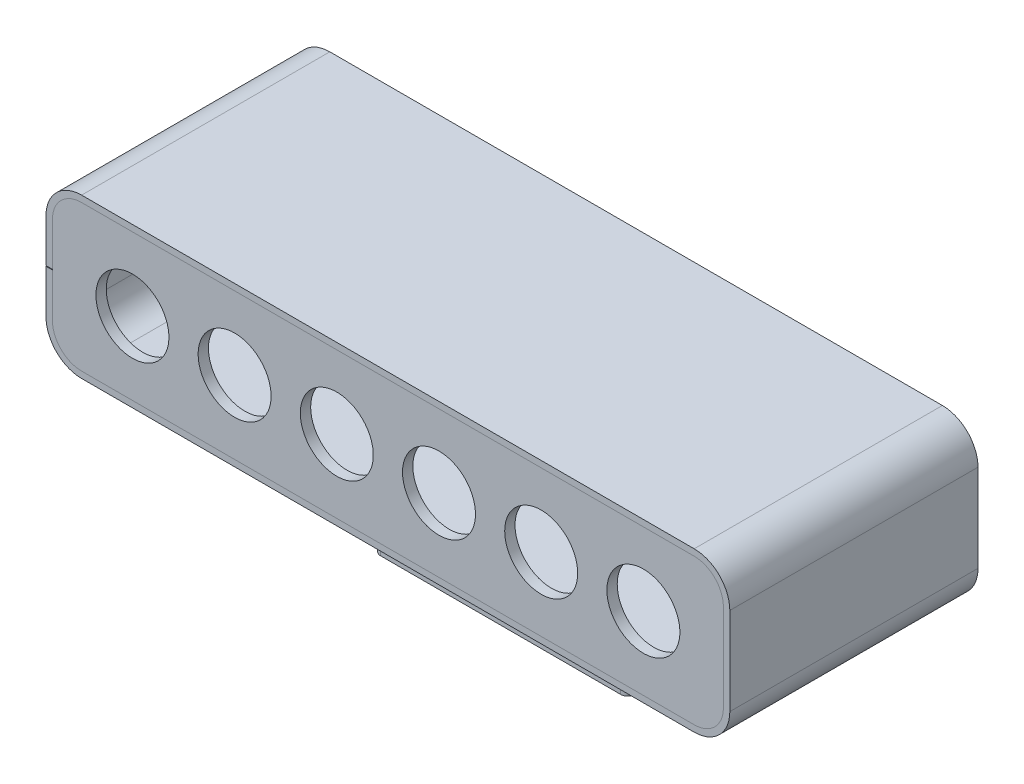
SolidWorks part; units mm, degrees
material "Acrylic (Medium-high impact)"
ref_plane "Front" through (0, 0, 0) normal (0, 0, 1) x (1, 0, 0)
ref_plane "Top" through (0, 0, 0) normal (0, 1, 0) x (1, 0, 0)
ref_plane "Right" through (0, 0, 0) normal (1, 0, 0) x (0, 0, -1)
sketch "Sketch5" plane through (0, 0, 0) normal (0, 1, 0) x (1, 0, 0)
  line L1 (0, 0) -> (-692.15, 0)
  line L2 (0, 0) -> (0, 107.95)
  line L3 (0, 107.95) -> (-692.15, 107.95)
  line L4 (-692.15, 0) -> (-692.15, 107.95)
  dimension "D1" = 107.95
  dimension "D2" = 692.15
extrude "Boss-Extrude4" [suppressed] add sketch "Sketch5" along normal blind 2.794
sketch "Sketch1" plane through (0, 0, 0) normal (0, 0, 1) x (1, 0, 0)
  line L1 (-145.923, 31.75) -> (145.923, 31.75)
  line L2 (-145.923, 31.75) -> (-145.923, -31.75)
  line L3 (-145.923, -31.75) -> (145.923, -31.75)
  line L4 (145.923, 31.75) -> (145.923, -31.75)
  line L5 (-145.923, 31.75) -> (145.923, -31.75) construction
  line L6 (-145.923, -31.75) -> (145.923, 31.75) construction
  point P0 (0, 0)
  dimension "D1" = 291.846
  dimension "D2" = 63.5
extrude "Boss-Extrude1" add sketch "Sketch1" along normal blind 4.4958
fillet "Fillet1" radius 12.7 4 edges at (-145.923, -31.75, 2.2479) (145.923, -31.75, 2.2479) (145.923, 31.75, 2.2479) (-145.923, 31.75, 2.2479)
sketch "Sketch3" plane through (0, 0, 0) normal (0, 0, 1) x (1, 0, 0)
  line L0 (133.223, 34.544) -> (-133.223, 34.544)
  line L1 (-148.717, 19.05) -> (-148.717, 0.254)
  line L2 (-133.223, -34.544) -> (133.223, -34.544)
  line L3 (148.717, -19.05) -> (148.717, 19.05)
  line L4 (-133.223, -31.75) -> (133.223, -31.75)
  line L5 (-145.923, 19.05) -> (-145.923, -19.05)
  line L6 (133.223, 31.75) -> (-133.223, 31.75)
  line L7 (145.923, -19.05) -> (145.923, 19.05)
  line L8 (-133.223, -31.75) -> (133.223, -31.75)
  line L9 (-145.923, 19.05) -> (-145.923, 0.254)
  line L10 (133.223, 31.75) -> (-133.223, 31.75)
  line L11 (145.923, -19.05) -> (145.923, 19.05)
  line L12 (-145.923, 0) -> (-148.717, 0)
  line L13 (-145.923, 0.254) -> (-148.717, 0.254)
  line L14 (-145.923, 0) -> (-145.923, -19.05)
  line L15 (-145.923, 19.05) -> (-145.923, -19.05) construction
  line L16 (-148.717, 0) -> (-148.717, -19.05)
  line L17 (-148.717, 19.05) -> (-148.717, -19.05) construction
  line L18 (-145.923, 19.05) -> (-145.923, -19.05) construction
  arc A0 (-133.223, 34.544) -> (-148.717, 19.05) centre (-133.223, 19.05) ccw
  arc A1 (-148.717, -19.05) -> (-133.223, -34.544) centre (-133.223, -19.05) ccw
  arc A2 (133.223, -34.544) -> (148.717, -19.05) centre (133.223, -19.05) ccw
  arc A3 (148.717, 19.05) -> (133.223, 34.544) centre (133.223, 19.05) ccw
  arc A4 (-145.923, -19.05) -> (-133.223, -31.75) centre (-133.223, -19.05) ccw
  arc A5 (-133.223, 31.75) -> (-145.923, 19.05) centre (-133.223, 19.05) ccw
  arc A6 (145.923, 19.05) -> (133.223, 31.75) centre (133.223, 19.05) ccw
  arc A7 (133.223, -31.75) -> (145.923, -19.05) centre (133.223, -19.05) ccw
  arc A8 (-145.923, -19.05) -> (-133.223, -31.75) centre (-133.223, -19.05) ccw
  arc A9 (-133.223, 31.75) -> (-145.923, 19.05) centre (-133.223, 19.05) ccw
  arc A10 (145.923, 19.05) -> (133.223, 31.75) centre (133.223, 19.05) ccw
  arc A11 (133.223, -31.75) -> (145.923, -19.05) centre (133.223, -19.05) ccw
  dimension "D3" = 0.254
  dimension "D1" = 0
  dimension "D2" = 2.794
extrude "Boss-Extrude2" add sketch "Sketch3" along normal blind 107.95 separate body
sketch "Sketch4" plane through (0, 0, 107.95) normal (0, 0, 1) x (1, 0, 0)
  line L4 (-145.923, 19.05) -> (-145.923, -19.05)
  line L5 (-133.223, -31.75) -> (133.223, -31.75)
  line L6 (145.923, -19.05) -> (145.923, 19.05)
  line L7 (133.223, 31.75) -> (-133.223, 31.75)
  line L8 (-145.923, 19.05) -> (-145.923, -19.05)
  line L9 (-133.223, -31.75) -> (133.223, -31.75)
  line L10 (145.923, -19.05) -> (145.923, 19.05)
  line L11 (133.223, 31.75) -> (-133.223, 31.75)
  arc A4 (-145.923, -19.05) -> (-133.223, -31.75) centre (-133.223, -19.05) ccw
  arc A5 (133.223, -31.75) -> (145.923, -19.05) centre (133.223, -19.05) ccw
  arc A6 (145.923, 19.05) -> (133.223, 31.75) centre (133.223, 19.05) ccw
  arc A7 (-133.223, 31.75) -> (-145.923, 19.05) centre (-133.223, 19.05) ccw
  arc A8 (-145.923, -19.05) -> (-133.223, -31.75) centre (-133.223, -19.05) ccw
  arc A9 (133.223, -31.75) -> (145.923, -19.05) centre (133.223, -19.05) ccw
  arc A10 (145.923, 19.05) -> (133.223, 31.75) centre (133.223, 19.05) ccw
  arc A11 (-133.223, 31.75) -> (-145.923, 19.05) centre (-133.223, 19.05) ccw
  dimension "D1" = 0
extrude "Boss-Extrude3" add sketch "Sketch4" against normal blind 4.4958 separate body
sketch "Sketch2" plane through (0, 0, 0) normal (0, 0, -1) x (-1, 0, 0)
  line L0 (22.225, 0) -> (-22.225, 0) construction
  line L1 (22.225, 0) -> (66.675, 0) construction
  line L2 (66.675, 0) -> (111.125, 0) construction
  line L3 (-22.225, 0) -> (-66.675, 0) construction
  line L4 (-66.675, 0) -> (-111.125, 0) construction
  line L5 (-111.125, 0) -> (-127, 0) construction
  line L6 (111.125, 0) -> (127, 0) construction
  circle A0 centre (-111.125, 0) radius 15.875
  circle A1 centre (-66.675, 0) radius 15.875
  circle A2 centre (-22.225, 0) radius 15.875
  circle A3 centre (22.225, 0) radius 15.875
  circle A4 centre (66.675, 0) radius 15.875
  circle A5 centre (111.125, 0) radius 15.875
  dimension "D1" = 31.75
  dimension "D2" = 254
extrude "Cut-Extrude1" cut sketch "Sketch2" against normal through all
sketch "Sketch6" plane through (0, -34.544, 0) normal (0, -1, 0) x (1, 0, 0)
  line L0 (0, 0) -> (0, 31.369) construction
  line L1 (-133.223, 0) -> (133.223, 0) construction
  line L2 (-52.705, 55.928) -> (-52.705, 6.81)
  line L3 (-52.245, 58.928) -> (52.245, 58.928)
  line L4 (-55.245, 55.928) -> (-55.245, 6.81)
  line L5 (-52.245, 3.81) -> (52.245, 3.81)
  line L6 (55.245, 55.928) -> (55.245, 6.81)
  line L7 (-55.245, 58.928) -> (55.245, 3.81) construction
  line L8 (-55.245, 3.81) -> (55.245, 58.928) construction
  line L9 (-52.245, 6.35) -> (52.245, 6.35)
  line L10 (52.705, 55.928) -> (52.705, 6.81)
  line L11 (-52.245, 56.388) -> (52.245, 56.388)
  arc A0 (-55.245, 6.81) -> (-52.245, 3.81) centre (-52.245, 6.81) ccw
  arc A1 (55.245, 6.81) -> (52.245, 3.81) centre (52.245, 6.81) cw
  arc A2 (55.245, 55.928) -> (52.245, 58.928) centre (52.245, 55.928) ccw
  arc A3 (-52.245, 58.928) -> (-55.245, 55.928) centre (-52.245, 55.928) ccw
  arc A4 (-52.705, 6.81) -> (-52.245, 6.35) centre (-52.245, 6.81) ccw
  arc A5 (52.705, 6.81) -> (52.245, 6.35) centre (52.245, 6.81) cw
  arc A6 (52.705, 55.928) -> (52.245, 56.388) centre (52.245, 55.928) ccw
  arc A7 (-52.245, 56.388) -> (-52.705, 55.928) centre (-52.245, 55.928) ccw
  dimension "D4" = 3
  dimension "D1" = 110.49
  dimension "D2" = 55.118
  dimension "D3" = 3.81
  dimension "D5" = 2.54
extrude "Boss-Extrude5" add sketch "Sketch6" along normal blind 50.8 separate body
sketch "Sketch7" plane through (0, 0, 0) normal (0, 0, -1) x (-1, 0, 0)
  line L0 (0, 0) -> (-52.3875, 0) construction
  line L1 (0, 0) -> (52.3875, 0) construction
  circle A0 centre (-52.3875, 0) radius 3.175
  circle A1 centre (52.3875, 0) radius 3.175
  dimension "D1" = 6.35
  dimension "D2" = 104.775
extrude "Cut-Extrude2" cut sketch "Sketch7" against normal up to next (4.4958 mm away)
sketch "Sketch8" plane through (0, -34.544, 0) normal (0, -1, 0) x (1, 0, 0)
  line L0 (0, 3.81) -> (0, 58.928) construction
  line L1 (-52.245, 3.81) -> (52.245, 3.81) construction
  line L2 (52.245, 58.928) -> (-52.245, 58.928) construction
  line L4 (-46.355, 53.594) -> (46.355, 53.594)
  line L5 (-50.165, 49.784) -> (-50.165, 12.954)
  line L6 (-46.355, 9.144) -> (46.355, 9.144)
  line L7 (50.165, 49.784) -> (50.165, 12.954)
  line L8 (-50.165, 53.594) -> (50.165, 9.144) construction
  line L9 (-50.165, 9.144) -> (50.165, 53.594) construction
  arc A0 (-50.165, 12.954) -> (-46.355, 9.144) centre (-46.355, 12.954) ccw
  arc A1 (50.165, 12.954) -> (46.355, 9.144) centre (46.355, 12.954) cw
  arc A2 (50.165, 49.784) -> (46.355, 53.594) centre (46.355, 49.784) ccw
  arc A3 (-46.355, 53.594) -> (-50.165, 49.784) centre (-46.355, 49.784) ccw
  point P6 (0, 31.369)
  dimension "D3" = 3.81
  dimension "D1" = 100.33
  dimension "D2" = 44.45
extrude "Cut-Extrude3" cut sketch "Sketch8" against normal up to next (2.794 mm away)
sketch "Sketch9" plane through (0, -34.544, 0) normal (0, -1, 0) x (1, 0, 0)
  line L1 (-120.717, 25) -> (-120.717, 0) construction
  line L5 (-133.223, 0) -> (133.223, 0) construction
  line L6 (-148.717, 107.95) -> (-148.717, 0) construction
  circle A0 centre (-120.717, 25) radius 15.875
  point P0 (-113.4335, 0)
  dimension "D1" = 31.75
  dimension "D2" = 25
  dimension "D3" = 28
extrude "Cut-Extrude4" cut sketch "Sketch9" along normal through all from surface starting at face at (0, 31.75, 53.975)
sketch "Sketch10" plane through (0, -34.544, 0) normal (0, -1, 0) x (1, 0, 0)
  circle A0 centre (63.5, 50.8) radius 1.7463
  circle A1 centre (63.5, 12.7) radius 1.7463
  circle A2 centre (-63.5, 50.8) radius 1.7462
  circle A3 centre (-63.5, 12.7) radius 1.7462
  arc A5 (-61.7042, 48.1817) -> (-60.3345, 51.046) centre (-63.5, 50.8) ccw construction
  arc A6 (-63.8073, 9.5399) -> (-60.9169, 10.8538) centre (-63.5, 12.7) ccw construction
  circle A7 centre (63.5, 50.8) radius 1.4732 construction
  circle A8 centre (63.5, 12.7) radius 1.4732 construction
  dimension "D1" = 3.4925
extrude "Cut-Extrude5" cut sketch "Sketch10" against normal up to next (2.794 mm away)
sketch "Sketch11" [suppressed] plane through (0, -31.75, 0) normal (0, 1, 0) x (1, 0, 0)
  line L0 (-133.223, -107.95) -> (-133.223, 0) construction
  line L1 (-133.223, -107.95) -> (-133.223, 0)
  line L2 (133.223, -107.95) -> (133.223, 0) construction
  line L3 (133.223, -107.95) -> (133.223, 0)
  line L4 (133.223, -107.95) -> (148.717, -107.95)
  line L5 (148.717, -107.95) -> (148.717, 0)
  line L6 (148.717, 0) -> (133.223, 0)
  line L7 (-133.223, 0) -> (-148.717, 0)
  line L8 (-148.717, 0) -> (-148.717, -107.95)
  line L9 (-148.717, -107.95) -> (-133.223, -107.95)
extrude "Cut-Extrude6" [suppressed] cut sketch "Sketch11" along normal through all
sketch "Sketch12" [suppressed] plane through (0, -31.75, 0) normal (0, 1, 0) x (1, 0, 0)
  line L0 (-133.223, -107.95) -> (-133.223, 0) construction
  line L1 (-133.223, -107.95) -> (-133.223, 0)
  line L2 (133.223, -107.95) -> (133.223, 0) construction
  line L3 (133.223, -107.95) -> (133.223, 0)
  line L4 (-142.0985, 0) -> (-142.0985, -107.95) construction
  line L5 (142.0985, 0) -> (-142.0985, 0) construction
  line L6 (142.0985, -107.95) -> (142.0985, 0) construction
  line L7 (142.0985, -107.95) -> (-142.0985, -107.95) construction
  line L8 (-142.0985, 0) -> (-142.0985, -107.95)
  line L9 (142.0985, 0) -> (133.223, 0)
  line L10 (142.0985, -107.95) -> (142.0985, 0)
  line L11 (142.0985, -107.95) -> (133.223, -107.95)
  line L12 (-133.223, -107.95) -> (-142.0985, -107.95)
  line L13 (-133.223, 0) -> (-142.0985, 0)
extrude "Cut-Extrude7" [suppressed] cut sketch "Sketch12" against normal through all
sketch "Sketch13" [suppressed] plane through (0, 34.544, 0) normal (0, 1, 0) x (1, 0, 0)
  line L4 (133.223, 0) -> (-133.223, 0)
  line L5 (-133.223, 0) -> (-133.223, -107.95)
  line L6 (-133.223, -107.95) -> (133.223, -107.95)
  line L7 (133.223, -107.95) -> (133.223, 0)
  line L8 (133.223, 0) -> (-133.223, 0)
  line L9 (-133.223, 0) -> (-133.223, -107.95)
  line L10 (-133.223, -107.95) -> (133.223, -107.95)
  line L11 (133.223, -107.95) -> (133.223, 0)
  dimension "D1" = 0
extrude "Cut-Extrude8" [suppressed] cut sketch "Sketch13" against normal up to surface (2.794 mm away) up to face at (-44.9692, 31.75, 44.3167)
sketch "Sketch14" [suppressed] plane through (0, -31.75, 0) normal (0, 1, 0) x (1, 0, 0)
  line L1 (-133.223, -107.95) -> (-171.323, -107.95)
  line L2 (-133.223, -107.95) -> (-133.223, 0)
  line L3 (-133.223, 0) -> (-171.323, 0)
  line L4 (-171.323, -107.95) -> (-171.323, 0)
  dimension "D1" = 38.1
sketch "Sketch15" [suppressed] plane through (0, -31.75, 0) normal (0, 1, 0) x (1, 0, 0)
  line L0 (-133.223, -107.95) -> (-133.223, 0) construction
  line L1 (133.223, -107.95) -> (558.927, -107.95)
  line L2 (133.223, -107.95) -> (133.223, 0)
  line L3 (133.223, 0) -> (558.927, 0)
  line L4 (558.927, -107.95) -> (558.927, 0)
  dimension "D1" = 692.15
extrude "Boss-Extrude6" [suppressed] add sketch "Sketch15" against normal up to surface (2.794 mm away) up to face at (65.2463, -34.544, 12.7)
